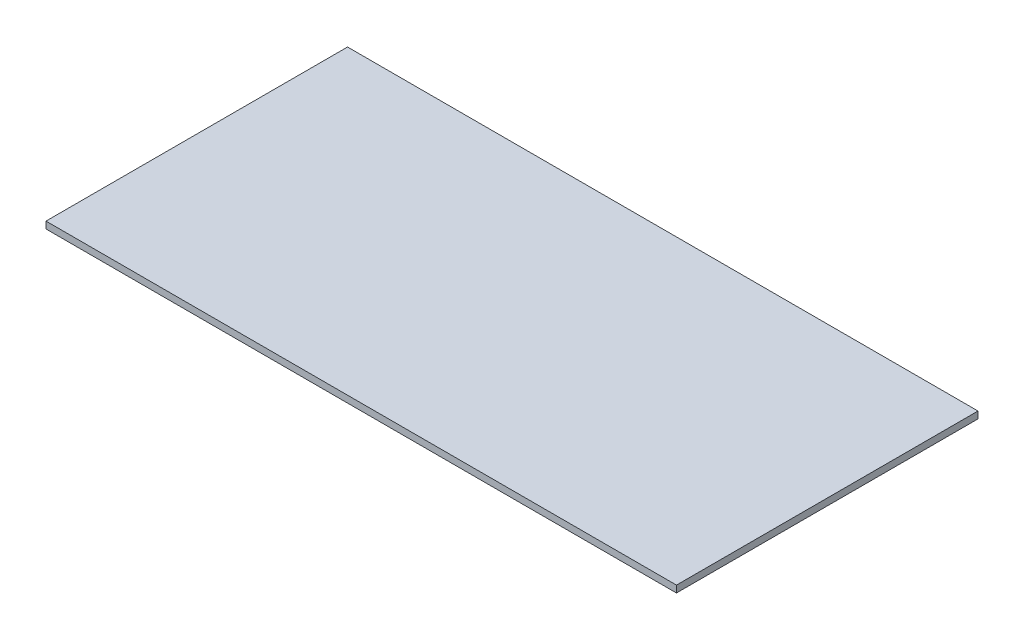
SolidWorks part; units mm, degrees
ref_plane "Front Plane" through (0, 0, 0) normal (0, 0, 1) x (1, 0, 0)
ref_plane "Top Plane" through (0, 0, 0) normal (0, 1, 0) x (1, 0, 0)
ref_plane "Right Plane" through (0, 0, 0) normal (1, 0, 0) x (0, 0, -1)
sketch "Sketch1" plane through (0, 0, 0) normal (0, 1, 0) x (1, 0, 0)
  line L1 (-462.2254, 74.056) -> (121.9746, 74.056)
  line L2 (-462.2254, 74.056) -> (-462.2254, -205.344)
  line L3 (-462.2254, -205.344) -> (121.9746, -205.344)
  line L4 (121.9746, 74.056) -> (121.9746, -205.344)
  dimension "D1" = 584.2
  dimension "D2" = 279.4
extrude "Boss-Extrude1" add sketch "Sketch1" along normal blind 6.35
